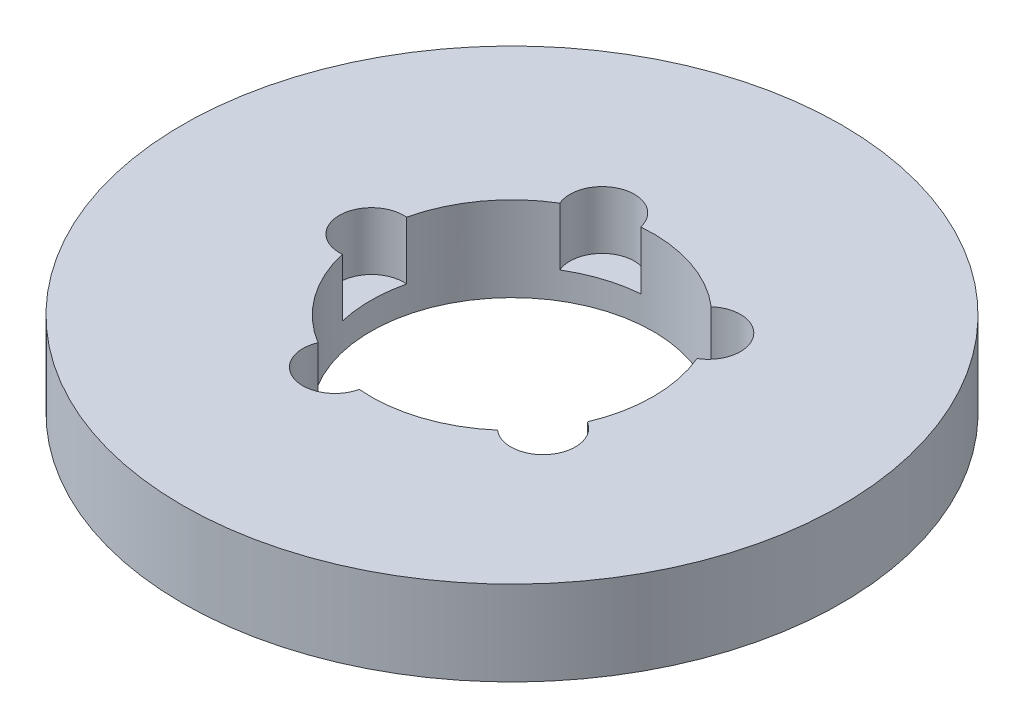
SolidWorks part; units mm, degrees
ref_plane "Front Plane" through (0, 0, 0) normal (0, 0, 1) x (1, 0, 0)
ref_plane "Top Plane" through (0, 0, 0) normal (0, 1, 0) x (1, 0, 0)
ref_plane "Right Plane" through (0, 0, 0) normal (1, 0, 0) x (0, 0, -1)
sketch "Sketch1" plane through (0, 0, 0) normal (0, 1, 0) x (1, 0, 0)
  circle A0 centre (0, 0) radius 70
  dimension "FLANGE_OD" = 140
extrude "Boss-Extrude1" add sketch "Sketch1" along normal blind 18
sketch "Sketch2" plane through (0, 0, 0) normal (0, 1, 0) x (1, 0, 0)
  circle A0 centre (0, 0) radius 30
  dimension "BORE_D" = 60
extrude "Cut-Extrude1" cut sketch "Sketch2" along normal through all
sketch "Sketch3" plane through (0, 18, 0) normal (0, 1, 0) x (1, 0, 0)
  circle A0 centre (0, 0) radius 29.8363 construction
  circle A1 centre (-29.8363, 0) radius 6.8528
  dimension "BOLT_D" = 13.7055
  dimension "BOLT_PCD" = 59.6726
extrude "Cut-Extrude2" cut sketch "Sketch3" against normal blind 12.2991
pattern_circular "CirPattern1" count 5 over 360 about axis through (0, 0, 0) along (0, 1, 0) of "Cut-Extrude2"
